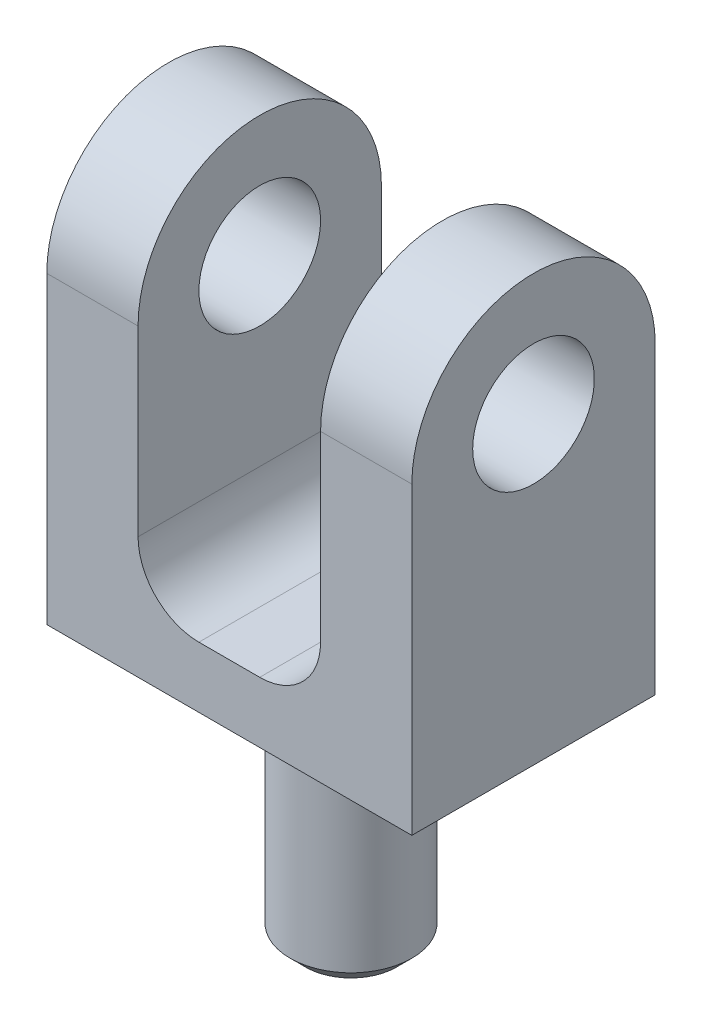
SolidWorks part; units mm, degrees
material "6061 Alloy"
ref_plane "Front Plane" through (0, 0, 0) normal (0, 0, 1) x (1, 0, 0)
ref_plane "Top Plane" through (0, 0, 0) normal (0, 1, 0) x (1, 0, 0)
ref_plane "Right Plane" through (0, 0, 0) normal (1, 0, 0) x (0, 0, -1)
sketch "Sketch1" plane through (0, 0, 0) normal (1, 0, 0) x (0, 0, -1)
  line L0 (-6.35, 0) -> (-6.35, -15.875)
  line L1 (-6.35, -15.875) -> (6.35, -15.875)
  line L2 (6.35, -15.875) -> (6.35, 0)
  line L3 (0, 0) -> (0, -15.875) construction
  circle A0 centre (0, 0) radius 3.175
  arc A1 (-6.35, 0) -> (6.35, 0) centre (0, 0) cw
  dimension "D1" = 6.35
  dimension "D2" = 6.35
  dimension "D3" = 15.875
extrude "Boss-Extrude1" add sketch "Sketch1" along normal mid plane 19.05
sketch "Sketch2" plane through (0, -15.875, 0) normal (0, -1, 0) x (1, 0, 0)
  line L0 (-9.525, 0) -> (9.525, 0) construction
  line L1 (-9.525, 6.35) -> (-9.525, -6.35) construction
  line L2 (9.525, 6.35) -> (9.525, -6.35) construction
  circle A0 centre (0, 0) radius 3.175
  dimension "D1" = 6.35
extrude "Boss-Extrude2" add sketch "Sketch2" along normal blind 12.7
chamfer "Chamfer1" distance 0.7937 angle 45 1 edges at (0, -28.575, -3.175)
sketch "Sketch3" plane through (0, 0, 0) normal (0, 0, 1) x (1, 0, 0)
  line L0 (9.525, 6.35) -> (-9.525, 6.35) construction
  line L1 (-4.7625, -12.7) -> (4.7625, -12.7)
  line L2 (-4.7625, -12.7) -> (-4.7625, 6.35)
  line L3 (-4.7625, 6.35) -> (4.7625, 6.35)
  line L4 (4.7625, -12.7) -> (4.7625, 6.35)
  line L5 (0, -12.7) -> (0, 6.35) construction
  dimension "D1" = 9.525
  dimension "D2" = 19.05
extrude "Cut-Extrude1" cut sketch "Sketch3" against normal through all and the other way through all
fillet "Fillet1" radius 3.175 2 edges at (-4.7625, -12.7, 0) (4.7625, -12.7, 0)
